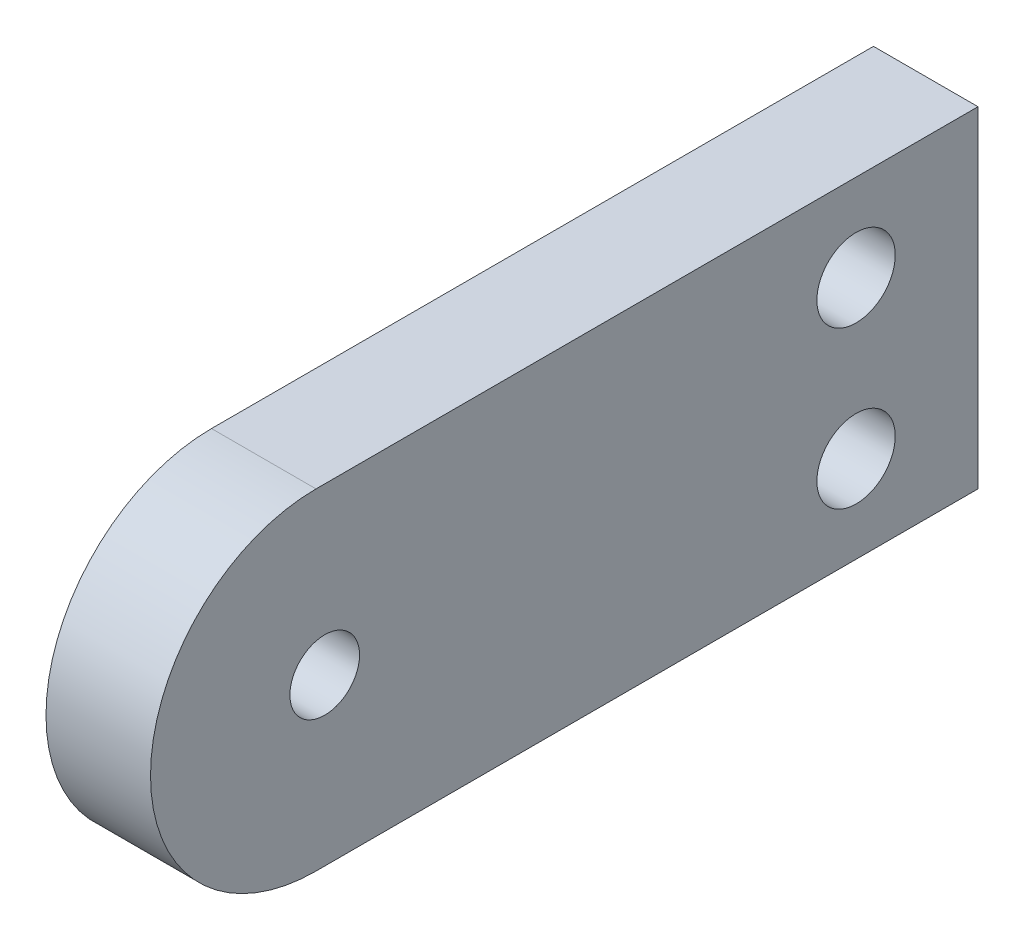
SolidWorks part; units mm, degrees
ref_plane "前视基准面" through (0, 0, 0) normal (0, 0, 1) x (1, 0, 0)
ref_plane "上视基准面" through (0, 0, 0) normal (0, 1, 0) x (1, 0, 0)
ref_plane "右视基准面" through (0, 0, 0) normal (1, 0, 0) x (0, 0, -1)
other "Configuration Table"
sketch "草图1" plane through (0, 0, 0) normal (1, 0, 0) x (0, 0, -1)
  line L0 (-150, 0) -> (150, 0) construction
  line L1 (-125, 14.5) -> (125, 14.5)
  line L2 (-125, 14.5) -> (-125, -14.5)
  line L3 (-125, -14.5) -> (125, -14.5)
  line L4 (125, 14.5) -> (125, -14.5)
  line L5 (-72.5, 29.5) -> (-72.5, 25.5)
  line L6 (-75, 14.5) -> (-45, 14.5)
  line L7 (-75, 14.5) -> (-75, 29.5)
  line L8 (-120, 10.8586) -> (120, 10.8586)
  line L9 (-120, 10.8586) -> (-120, -10.8586)
  line L10 (-120, -10.8586) -> (120, -10.8586)
  line L11 (120, 10.8586) -> (120, -10.8586)
  line L12 (-120, 10.8586) -> (120, -10.8586) construction
  line L13 (-120, -10.8586) -> (120, 10.8586) construction
  line L14 (-75, 29.5) -> (-45, 29.5)
  line L15 (-45, 14.5) -> (-45, 29.5)
  line L16 (-15, 14.5) -> (15, 14.5)
  line L17 (-15, 14.5) -> (-15, 29.5)
  line L18 (-15, 29.5) -> (15, 29.5)
  line L19 (15, 14.5) -> (15, 29.5)
  line L20 (45, 14.5) -> (75, 14.5)
  line L21 (45, 14.5) -> (45, 29.5)
  line L22 (45, 29.5) -> (75, 29.5)
  line L23 (75, 14.5) -> (75, 29.5)
  line L24 (-47.5, 29.5) -> (-47.5, 25.5)
  line L25 (-12.5, 29.5) -> (-12.5, 25.5)
  line L26 (12.5, 29.5) -> (12.5, 25.5)
  line L27 (47.5, 29.5) -> (47.5, 25.5)
  line L29 (72.5, 25.5) -> (72.5, 29.5)
  circle A2 centre (-67.5, -10.8586) radius 2
  circle A3 centre (-22.5, -10.8586) radius 2
  circle A4 centre (22.5, -10.8586) radius 2
  circle A5 centre (-60, 25.5) radius 2
  circle A6 centre (67.5, -10.8586) radius 2
  circle A7 centre (0, 25.5) radius 2
  circle A8 centre (60, 25.5) radius 2
  circle A9 centre (-60, 25.5) radius 12.5
  circle A10 centre (0, 25.5) radius 12.5
  circle A11 centre (60, 25.5) radius 12.5
  circle A12 centre (-67.5, -10.8586) radius 12.5
  circle A13 centre (-22.5, -10.8586) radius 12.5
  circle A14 centre (22.5, -10.8586) radius 12.5
  circle A15 centre (67.5, -10.8586) radius 12.5
  circle A16 centre (150, 0) radius 2
  circle A17 centre (-150, 0) radius 2
  circle A18 centre (-150, 0) radius 3.1
  point P10 (0, 0)
  point P12 (-125, 0)
  point P56 (-60, 29.5)
  point P62 (0, 29.5)
  point P64 (60, 29.5)
  dimension "D2" = 5
  dimension "D4" = 25
  dimension "D8" = 4
  dimension "D18" = 4
  dimension "D22" = 6.2
  dimension "D1" = 300
  dimension "D3" = 5
  dimension "D5" = 14.5
  dimension "D6" = 120
  dimension "D7" = 10.8586
  dimension "D9" = 52.5
  dimension "D10" = 45
  dimension "D11" = 45
  dimension "D12" = 45
  dimension "D13" = 60
  dimension "D14" = 60
  dimension "D15" = 60
  dimension "D16" = 60
  dimension "D17" = 52.5
  dimension "D19" = 30
  dimension "D20" = 4
  dimension "D21" = 15
extrude "凸台-拉伸1" add sketch "草图1" along normal blind 28 contours L1 L4 L3 L2 | L14 L15 L6 L7 | L18 L19 L16 L17 | L22 L23 L20 L21
extrude "切除-拉伸1" cut sketch "草图1<3>" along normal through all contours A2 | A3 | A4 | A6 | A8 | A7 | A5
sketch "草图1<3>" plane through (0, 0, 0) normal (1, 0, 0) x (0, 0, -1) same geometry as "草图1"
extrude "切除-拉伸2" cut sketch "草图1<5>" along normal offset from surface (24 mm away) 2 from offset 2 contours A9 L14 L5 | A9 L24 L14 | A10 L18 L25 | A10 L26 L18 | A11 L22 L27 | A11 L29 L22 | A12 | A9 | A13 | A10 | A14 | A11 | A15 region at (0, 28.5053, 72.3037) region at (0, 28.5053, 47.6963) region at (0, 28.5053, 12.3037) region at (0, 28.5053, -12.3037) region at (0, 28.5053, -47.6963) region at (0, 28.5053, -72.3037) up to face at (28, -10.8586, 65.5)
sketch "草图1<5>" plane through (0, 0, 0) normal (1, 0, 0) x (0, 0, -1) same geometry as "草图1"
sketch "草图3" plane through (0, 0, 125) normal (0, 0, 1) x (1, 0, 0)
  line L0 (28, 14.5) -> (28, -14.5) construction
  line L1 (28, 9.5) -> (22, 9.5)
  line L2 (28, 9.5) -> (28, -9.5)
  line L3 (28, -9.5) -> (22, -9.5)
  line L4 (22, 9.5) -> (22, -9.5)
  line L5 (28, 14.5) -> (0, 14.5) construction
  line L6 (28, -14.5) -> (0, -14.5) construction
  line L7 (0, 14.5) -> (0, -14.5) construction
  line L8 (0, 9.5) -> (6, 9.5)
  line L9 (0, 9.5) -> (0, -9.5)
  line L10 (0, -9.5) -> (6, -9.5)
  line L11 (6, 9.5) -> (6, -9.5)
  dimension "D1" = 6
  dimension "D2" = 5
  dimension "D3" = 5
extrude "凸台-拉伸2" add sketch "草图3" along normal blind 35 contours L1 L4 L3 L2
extrude "凸台-拉伸3" add sketch "草图3<3>" along normal blind 35 contours L2 L3 L4 L1 | L9 L10 L11 L8
sketch "草图3<3>" plane through (0, 0, 125) normal (0, 0, 1) x (1, 0, 0) same geometry as "草图3"
extrude "切除-拉伸3" cut sketch "草图1<6>" along normal through all contours A17
sketch "草图1<6>" plane through (0, 0, 0) normal (1, 0, 0) x (0, 0, -1) same geometry as "草图1"
extrude "切除-拉伸7" cut sketch "草图1<8>" along normal up to next contours A18
sketch "草图1<8>" plane through (0, 0, 0) normal (1, 0, 0) x (0, 0, -1) same geometry as "草图1"
fillet "圆角1" radius 9.5 4 edges at (25, 9.5, 160) (25, -9.5, 160) (3, -9.5, 160) (3, 9.5, 160)
fillet "圆角2" radius 5 2 edges at (14, -14.5, 125) (14, 14.5, 125)
sketch "草图4" plane through (0, 0, -125) normal (0, 0, -1) x (-1, 0, 0)
  line L1 (-28, 14.5) -> (0, 14.5) construction
  circle A0 centre (-14, 0) radius 5.1
  point P7 (-14, 14.5)
  dimension "D1" = 10.2
extrude "切除-拉伸4" cut sketch "草图4" against normal blind 31.5
extrude "切除-拉伸5" cut sketch "草图4<2>" against normal offset from surface (21.5 mm away) 10 flip side to cut up to face at (8.9, 0, -93.5)
sketch "草图4<2>" plane through (0, 0, -125) normal (0, 0, -1) x (-1, 0, 0) same geometry as "草图4"
sketch "草图5" plane through (0, 0, -103.5) normal (0, 0, -1) x (-1, 0, 0)
  line L0 (-28, 14.5) -> (0, 14.5) construction
  line L1 (-25.9, -12.4) -> (-2.1, -12.4)
  line L2 (-25.9, -12.4) -> (-25.9, 12.4)
  line L3 (-25.9, 12.4) -> (-2.1, 12.4)
  line L4 (-2.1, -12.4) -> (-2.1, 12.4)
  line L5 (-25.9, -12.4) -> (-2.1, 12.4) construction
  line L6 (-25.9, 12.4) -> (-2.1, -12.4) construction
  line L7 (0, -14.5) -> (0, 14.5) construction
  circle A0 centre (-14, 0) radius 5.1 construction
  point P0 (-14, 0)
  dimension "D1" = 2.1
  dimension "D2" = 2.1
extrude "切除-拉伸6" cut sketch "草图5" against normal blind 18 flip side to cut contours L3 L4 L1 L2
sketch "草图6" plane through (0, 14.5, 0) normal (0, 1, 0) x (1, 0, 0)
  circle A0 centre (7, 23.5) radius 0.75
  circle A1 centre (21, 35.5) radius 0.75
  circle A2 centre (7, -23.5) radius 0.75
  circle A3 centre (21, -35.5) radius 0.75
  dimension "D1" = 1.5
extrude "切除-拉伸8" cut sketch "草图6" against normal blind 4 contours A2 | A3 | A0 | A1
sketch "草图7" plane through (0, 14.5, 0) normal (0, 1, 0) x (1, 0, 0)
  circle A0 centre (7, -89.5) radius 0.75
  circle A1 centre (21.2, -110.5) radius 0.75
  dimension "D1" = 1.5
extrude "切除-拉伸9" cut sketch "草图7" against normal blind 4 contours A0 | A1
sketch "草图8" plane through (0, 0, 0) normal (-1, 0, 0) x (0, 0, 1)
  circle A0 centre (47, 4) radius 0.75
  circle A1 centre (2.499, -1.5) radius 0.75
  dimension "D1" = 1.5
extrude "切除-拉伸10" cut sketch "草图8" against normal blind 4
sketch "草图9" plane through (28, 0, 0) normal (1, 0, 0) x (0, 0, -1)
  circle A0 centre (-107.5, -0.5) radius 0.75
  circle A1 centre (-92.5, -0.5) radius 0.75
  dimension "D1" = 1.5
extrude "切除-拉伸11" cut sketch "草图9" against normal blind 4 contours A0 | A1
sketch "草图10" plane through (0, 0, 0) normal (-1, 0, 0) x (0, 0, 1)
  line L0 (30, 14.5) -> (0, -14.5)
  line L1 (45, 14.5) -> (15, 14.5) construction
  line L2 (120, -14.5) -> (-85.5, -14.5) construction
  line L3 (30, 14.5) -> (30, 45.5421)
  line L4 (30, 45.5421) -> (207.4503, 45.5421)
  line L5 (207.4503, 45.5421) -> (207.4503, -65.6361)
  line L6 (207.4503, -65.6361) -> (0, -65.6361)
  line L7 (0, -65.6361) -> (0, -14.5)
  line L8 (30, 45.5421) -> (-140.4585, 45.5421)
  line L9 (30, 14.5) -> (-10, 14.5)
  line L10 (30, 14.5) -> (30, -14.5)
  line L11 (30, -14.5) -> (-10, -14.5)
  line L12 (-10, 14.5) -> (-10, -14.5)
  line L13 (-140.4585, 45.5421) -> (-140.4585, -65.6361)
  line L14 (-140.4585, -65.6361) -> (-10, -65.6361)
  line L15 (-10, -65.6361) -> (-10, -14.5)
  circle M8 centre (2.499, -1.5) radius 0.75
  circle M12 centre (0, 25.5) radius 2
  circle M13 centre (-60, 25.5) radius 2
  circle M14 centre (-67.5, -10.8586) radius 2
  circle M15 centre (-22.5, -10.8586) radius 2
  line M17 (-85.5, 14.5) -> (-85.5, -14.5)
  line M18 (-85.5, -14.5) -> (120, -14.5)
  line M29 (45, 14.5) -> (15, 14.5)
  line M30 (15, 14.5) -> (15, 29.5)
  line M31 (15, 29.5) -> (-15, 29.5)
  line M32 (-15, 29.5) -> (-15, 14.5)
  line M33 (-15, 14.5) -> (-45, 14.5)
  line M34 (-45, 14.5) -> (-45, 29.5)
  line M35 (-45, 29.5) -> (-75, 29.5)
  line M36 (-75, 29.5) -> (-75, 14.5)
  line M37 (-75, 14.5) -> (-85.5, 14.5)
  dimension "D1" = 40
sketch "草图11" plane through (0, 0, 0) normal (1, 0, 0) x (0, 0, -1)
  line L0 (-30, 14.5) -> (0, -14.5) construction
  line L1 (-45, 14.5) -> (-15, 14.5) construction
  line L2 (-120, -14.5) -> (85.5, -14.5) construction
  circle A0 centre (-14.5301, 6.5) radius 0.75
  circle A1 centre (-1.0818, -6.5) radius 0.75
  circle A2 centre (-14.5301, 6.5) radius 2.5
  circle A3 centre (-1.0818, -6.5) radius 2.5
  circle A4 centre (-14.5301, 6.5) radius 1.8
  circle A5 centre (-1.0818, -6.5) radius 1.8
  circle A6 centre (5.4699, 6.5) radius 0.75
  circle A7 centre (5.4699, 6.5) radius 2.5
  circle A8 centre (5.4699, 6.5) radius 1.8
  dimension "D3" = 1.5
  dimension "D4" = 3.6
  dimension "D5" = 5
  dimension "D1" = 5
  dimension "D2" = 5
  dimension "D6" = 8
  dimension "D7" = 8
  dimension "D8" = 20
extrude "切除-拉伸12" cut sketch "草图11" along normal through all contours A1 | A0 | A6
extrude "切除-拉伸14" cut sketch "草图10" against normal through all contours L14 L15 L3 L8 L13 M18 M17 M37 M36 M35 M34 M33 M32 M31 M30 M29 | L12 L9 M30 M31 M32 M33 M34 M35 M36 M37 M17 M18 M12 M14 M15 M13 region at (0, 16.5351, 22.5) region at (0, 6.3937, -42.6633)
extrude "切除-拉伸15" cut sketch "草图10<5>" against normal blind 4.1 contours L9 L12 L0 M18 M29 M8 region at (0, 2.9108, 4.0037)
sketch "草图10<5>" plane through (0, 0, 0) normal (-1, 0, 0) x (0, 0, 1) same geometry as "草图10"
extrude "切除-拉伸16" cut sketch "草图10<6>" along normal blind 4.1 from surface contours L9 L12 L0 M18 M29 M8 | M8 region at (0, 2.9108, 4.0037) region at (0, -1.5, 2.499) starting at face at (28, 6.7692, 90.5389)
sketch "草图10<6>" plane through (0, 0, 0) normal (-1, 0, 0) x (0, 0, 1) same geometry as "草图10"
sketch "草图13" plane through (0, 14.5, 0) normal (0, 1, 0) x (1, 0, 0)
  line L0 (4.1, -30) -> (0, -30) construction
  line L1 (4.1, -30) -> (23.9, -30)
  line L2 (4.1, -30) -> (4.1, 10)
  line L3 (4.1, 10) -> (23.9, 10)
  line L4 (23.9, -30) -> (23.9, 10)
  line L5 (4.1, -30) -> (4.1, -5.9372) construction
extrude "切除-拉伸17" cut sketch "草图13" against normal blind 4.1
sketch "草图14" plane through (0, -14.5, 0) normal (0, -1, 0) x (1, 0, 0)
  line L0 (4.1, 0) -> (0, 0) construction
  line L1 (4.1, 0) -> (23.9, 0)
  line L2 (4.1, 0) -> (4.1, -10)
  line L3 (4.1, -10) -> (23.9, -10)
  line L4 (23.9, 0) -> (23.9, -10)
  line L5 (4.1, -10) -> (4.1, 0) construction
extrude "切除-拉伸18" cut sketch "草图14" against normal blind 4.1
sketch "草图15" plane through (0, 0, 0) normal (-1, 0, 0) x (0, 0, 1)
  line L0 (0, -10.4) -> (0, -14.5)
  line L1 (0, -14.5) -> (4.2414, -10.4)
  line L2 (30, 14.5) -> (0, -14.5) construction
  line L4 (4.2414, -10.4) -> (0, -10.4)
  line L5 (0, -10.4) -> (-10, -10.4) construction
extrude "切除-拉伸19" cut sketch "草图15" against normal through all
sketch "草图16" plane through (0, 29.5, 0) normal (0, 1, 0) x (1, 0, 0)
  line L0 (28, -75) -> (0, -75) construction
  line L1 (6, -77.5) -> (22, -77.5)
  line L2 (6, -77.5) -> (6, -72.5)
  line L3 (6, -72.5) -> (22, -72.5)
  line L4 (22, -77.5) -> (22, -72.5)
  line L5 (6, -77.5) -> (22, -72.5) construction
  line L6 (6, -72.5) -> (22, -77.5) construction
  line L7 (26, -72.5) -> (2, -72.5) construction
  line L8 (26, -47.5) -> (26, -72.5) construction
  line L9 (6, -72.5) -> (22, -72.5)
  line L10 (6, -72.5) -> (6, -60)
  line L11 (6, -60) -> (22, -60)
  line L12 (22, -72.5) -> (22, -60)
  point P0 (14, -75)
  point P7 (14, -75)
  point P14 (26, -60)
  line M10 (0, -75) -> (28, -75)
  line M13 (26, -72.5) -> (2, -72.5)
  dimension "D1" = 16
extrude "切除-拉伸20" cut sketch "草图16" against normal blind 3 contours L1 L4 L2 M10 | L4 L2 M10 M13 | L12 L11 L10 M13 region at (14, 29.5, 76.25) region at (14, 29.5, 73.75) region at (14, 29.5, 66.25)
sketch "草图18" plane through (28, 0, 0) normal (1, 0, 0) x (0, 0, -1)
  line L0 (-150.5, 9.5) -> (-125, 9.5) construction
  line L1 (-160, 9.5) -> (-112.5, 9.5)
  line L2 (-160, 9.5) -> (-160, -9.5)
  line L3 (-160, -9.5) -> (-112.5, -9.5)
  line L4 (-112.5, 9.5) -> (-112.5, -9.5)
  line L5 (-150.5, -9.5) -> (-125, -9.5) construction
  arc A0 (-150.5, 9.5) -> (-160, 0) centre (-150.5, 0) ccw construction
  circle A1 centre (-107.5, -0.5) radius 0.75 construction
  circle A2 centre (-119.5, 4.5) radius 1.5
  circle A3 centre (-119.5, 4.5) radius 0.75
  circle A4 centre (-119.5, 4.5) radius 2.25
  circle A5 centre (-119.5, -4.5) radius 0.75
  circle A6 centre (-119.5, -4.5) radius 1.5
  circle A7 centre (-119.5, -4.5) radius 2.25
  dimension "D1" = 5
  dimension "D2" = 4.5
  dimension "D3" = 3
  dimension "D4" = 1.5
  dimension "D5" = 7
  dimension "D6" = 5
  dimension "D7" = 5
extrude "切除-拉伸21" cut sketch "草图18" against normal through all flip side to cut contours L1 L4 L3 L2
extrude "切除-拉伸22" cut sketch "草图18<4>" against normal through all from surface contours L1 L4 L3 L2 starting at face at (22, 2, 150)
sketch "草图18<4>" plane through (28, 0, 0) normal (1, 0, 0) x (0, 0, -1) same geometry as "草图18"
extrude "切除-拉伸23" cut sketch "草图18<5>" against normal through all contours A2 | A6
sketch "草图18<5>" plane through (28, 0, 0) normal (1, 0, 0) x (0, 0, -1) same geometry as "草图18"
extrude "切除-拉伸24" cut sketch "草图18<6>" against normal offset from surface (4 mm away) 2 contours A4 | A7 up to face at (22, 4.5, 118)
sketch "草图18<6>" plane through (28, 0, 0) normal (1, 0, 0) x (0, 0, -1) same geometry as "草图18"
ref_plane "基准面1" through (-10, 0, 0) normal (1, 0, 0) x (0, 0, -1)
sketch "草图17" plane through (-10, 0, 0) normal (1, 0, 0) x (0, 0, -1)
  line L1 (-200, -100) -> (200, -100)
  line L2 (-200, -100) -> (-200, 100)
  line L3 (-200, 100) -> (200, 100)
  line L4 (200, -100) -> (200, 100)
  line L5 (-200, -100) -> (200, 100) construction
  line L6 (-200, 100) -> (200, -100) construction
  point P0 (0, 0)
  dimension "D1" = 400
  dimension "D2" = 200
